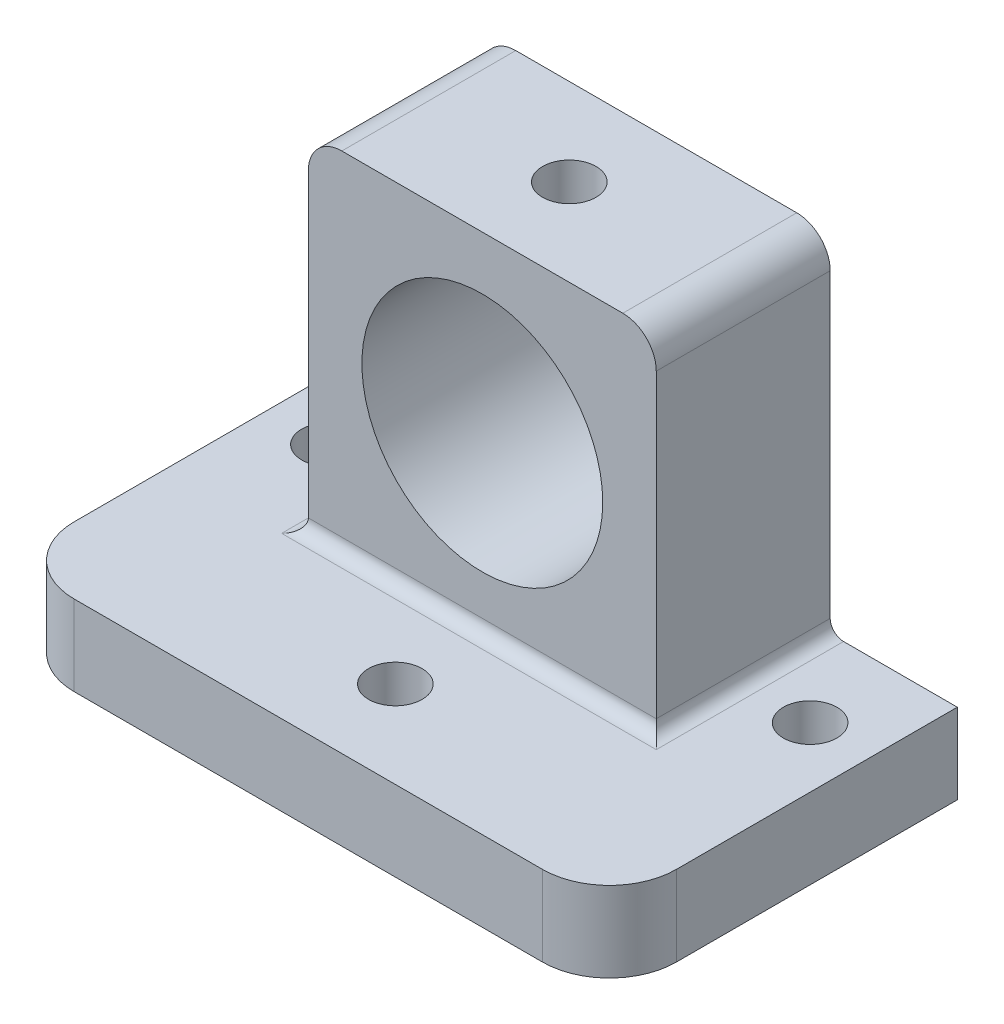
SolidWorks part; units mm, degrees
material "Alumina"
ref_plane "Front Plane" through (0, 0, 0) normal (0, 0, 1) x (1, 0, 0)
ref_plane "Top Plane" through (0, 0, 0) normal (0, 1, 0) x (1, 0, 0)
ref_plane "Right Plane" through (0, 0, 0) normal (1, 0, 0) x (0, 0, -1)
sketch "Sketch1" plane through (0, 0, 0) normal (0, 1, 0) x (1, 0, 0)
  line L0 (0, 0) -> (0, 20356.7438) construction
  line L1 (0, 0) -> (20356.7438, 0) construction
  line L2 (-22.5, -6.5) -> (22.5, -6.5) construction
  line L3 (-22.5, 0) -> (22.5, 0)
  line L4 (-22.5, 0) -> (-22.5, -21)
  line L5 (-17.5, -26) -> (17.5, -26)
  line L6 (22.5, 0) -> (22.5, -21)
  line L8 (-13, -13) -> (13, -13)
  line L9 (-13, -13) -> (-13, 0)
  line L10 (-13, 0) -> (13, 0)
  line L11 (13, -13) -> (13, 0)
  line L12 (-13, -13) -> (13, 0) construction
  line L13 (-13, 0) -> (13, -13) construction
  arc A0 (17.5, -26) -> (22.5, -21) centre (17.5, -21) ccw
  arc A1 (-22.5, -21) -> (-17.5, -26) centre (-17.5, -21) ccw
  circle A2 centre (-18, -6.5) radius 2
  circle A3 centre (18, -6.5) radius 2
  circle A4 centre (0, -19.5) radius 2
  point P9 (0, 0)
  point P22 (0, -6.5)
  dimension "D2" = 5
  dimension "D3" = 4
  dimension "D1" = 45
  dimension "D4" = 6.5
  dimension "D5" = 18
  dimension "D6" = 13
  dimension "D7" = 26
  dimension "D8" = 13
  dimension "D9" = 26
extrude "Boss-Extrude1" add sketch "Sketch1" along normal blind 6 contours L4 A1 L5 A0 L6 L3 L11 L8 L9 A4 A2 A3 region at (0, 0, 15.7453)
extrude "Boss-Extrude2" add sketch "Sketch1<3>" along normal blind 32 contours L8 L11 L3 L9 region at (0, 0, 6.5)
sketch "Sketch1<3>" plane through (0, 0, 0) normal (0, 1, 0) x (1, 0, 0) same geometry as "Sketch1"
fillet "Fillet1" radius 2.5 2 edges at (-13, 32, 6.5) (13, 32, 6.5)
sketch "Sketch2" plane through (0, 0, 13) normal (0, 0, 1) x (1, 0, 0)
  line L0 (0, 0) -> (0, 50000) construction
  line L1 (-10.5, 32) -> (10.5, 32) construction
  circle A0 centre (0, 19) radius 9
  dimension "D1" = 18
  dimension "D2" = 13
extrude "Cut-Extrude1" cut sketch "Sketch2" against normal through all
sketch "Sketch3" plane through (0, 32, 0) normal (0, 1, 0) x (1, 0, 0)
  line L0 (0, 0) -> (0, -50000) construction
  line L1 (-10.5, 0) -> (10.5, 0) construction
  circle A0 centre (0, -6.5) radius 2
  dimension "D1" = 4
  dimension "D2" = 6.5
extrude "Cut-Extrude2" cut sketch "Sketch3" against normal up to next
cosmetic thread "Cosmetic Thread1" parameters "D2"=5
fillet "Fillet2" radius 1 3 edges at (-13, 6, 6.5) (0, 6, 13) (13, 6, 6.5)
